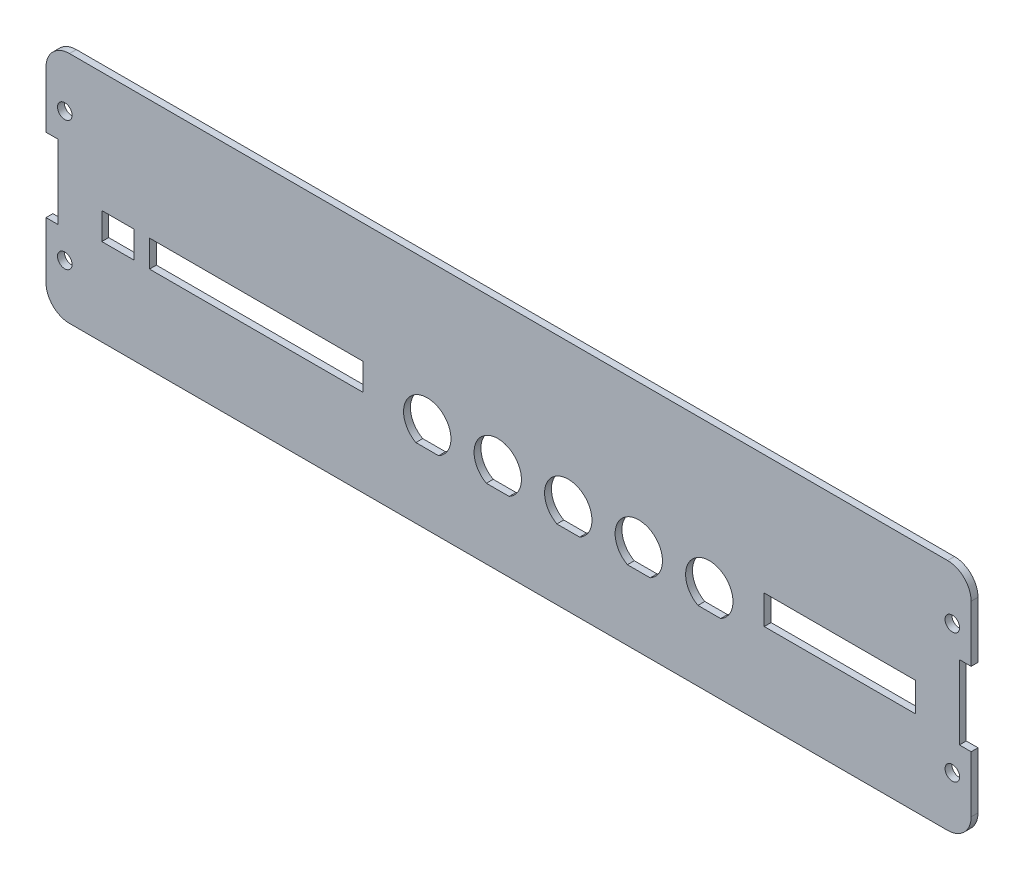
SolidWorks part; units mm, degrees
ref_plane "Front Plane" through (0, 0, 0) normal (0, 0, 1) x (1, 0, 0)
ref_plane "Top Plane" through (0, 0, 0) normal (0, 1, 0) x (1, 0, 0)
ref_plane "Right Plane" through (0, 0, 0) normal (1, 0, 0) x (0, 0, -1)
sketch "Sketch2" plane through (0, 0, 0) normal (0, 0, 1) x (1, 0, 0)
  line L0 (118.618, 31.5722) -> (-118.618, 31.5722)
  line L1 (-124.968, 25.2222) -> (-124.968, 9.9822)
  line L2 (-124.968, 9.9822) -> (-121.793, 9.9822)
  line L3 (-121.793, 9.9822) -> (-121.793, -9.9822)
  line L4 (0, 0) -> (0, 31.5722) construction
  line L5 (0, 0) -> (-121.793, 0) construction
  line L6 (124.968, 25.2222) -> (124.968, 9.9822)
  line L7 (124.968, 9.9822) -> (121.793, 9.9822)
  line L8 (121.793, 9.9822) -> (121.793, -9.9822)
  line L9 (124.968, -9.9822) -> (121.793, -9.9822)
  line L10 (124.968, -25.2222) -> (124.968, -9.9822)
  line L11 (-124.968, -9.9822) -> (-121.793, -9.9822)
  line L12 (-124.968, -25.2222) -> (-124.968, -9.9822)
  line L13 (118.618, -31.5722) -> (-118.618, -31.5722)
  arc A0 (-124.968, 25.2222) -> (-118.618, 31.5722) centre (-118.618, 25.2222) cw
  arc A1 (124.968, 25.2222) -> (118.618, 31.5722) centre (118.618, 25.2222) ccw
  arc A2 (124.968, -25.2222) -> (118.618, -31.5722) centre (118.618, -25.2222) cw
  arc A3 (-124.968, -25.2222) -> (-118.618, -31.5722) centre (-118.618, -25.2222) ccw
  point P22 (121.793, 0)
  point P25 (-124.968, -17.6022)
  dimension "D1" = 6.35
  dimension "D2" = 3.175
  dimension "D3" = 21.59
  dimension "D4" = 9.9822
  dimension "D5" = 249.936
extrude "MainBody" add sketch "Sketch2" along normal blind 1.8542
sketch "Sketch3" plane through (0, 0, 1.8542) normal (0, 0, 1) x (1, 0, 0)
  line L0 (118.618, 31.5722) -> (-118.618, 31.5722) construction
  line L2 (0, 31.5722) -> (0, 0) construction
  line L3 (0, 0) -> (-121.793, 0) construction
  line L4 (-121.793, 9.9822) -> (-121.793, -9.9822) construction
  circle A0 centre (-119.888, 17.4625) radius 1.9685
  circle A1 centre (119.888, 17.4625) radius 1.9685
  circle A2 centre (119.888, -17.4625) radius 1.9685
  circle A3 centre (-119.888, -17.4625) radius 1.9685
  dimension "D1" = 3.937
  dimension "D2" = 17.4625
  dimension "D3" = 119.888
extrude "MountHoles" cut sketch "Sketch3" against normal through all
ref_axis "MntTopLeft" through (-119.888, 17.4625, 0) along (0, 0, 1)
ref_axis "MntBottomLeft" through (-119.888, -17.4625, 0) along (0, 0, 1)
ref_axis "MntTopRight" through (119.888, 17.4625, 0) along (0, 0, 1)
ref_axis "MntBottomRight" through (119.888, -17.4625, 0) along (0, 0, 1)
ref_plane "ExtFront" through (0, 0, 1.8542) normal (0, 0, 1) x (1, 0, 0)
ref_plane "IntFront" through (0, 0, 0) normal (0, 0, -1) x (-1, 0, 0)
ref_plane "TBCenter" through (0, 0, 0) normal (0, 1, 0) x (1, 0, 0)
ref_plane "LRCenter" through (0, 0, 0) normal (-1, 0, 0) x (0, 0, 1)
sketch "Sketch4" plane through (0, 0, 1.8542) normal (0, 0, 1) x (1, 0, 0)
  line L12 (51.1533, -12.6575) -> (57.3047, -12.6575)
  line L13 (51.1533, -12.6575) -> (57.3047, -12.6575)
  line L14 (69.068, -0.7936) -> (69.068, -8.6476)
  line L15 (110.002, -0.7936) -> (69.068, -0.7936)
  line L16 (110.002, -8.6476) -> (110.002, -0.7936)
  line L17 (69.068, -8.6476) -> (110.002, -8.6476)
  line L18 (69.068, -0.7936) -> (69.068, -8.6476)
  line L19 (110.002, -0.7936) -> (69.068, -0.7936)
  line L20 (110.002, -8.6476) -> (110.002, -0.7936)
  line L21 (69.068, -8.6476) -> (110.002, -8.6476)
  line L24 (32.1033, -12.6575) -> (38.2547, -12.6575)
  line L25 (32.1033, -12.6575) -> (38.2547, -12.6575)
  line L28 (13.0533, -12.6575) -> (19.2047, -12.6575)
  line L29 (13.0533, -12.6575) -> (19.2047, -12.6575)
  line L31 (-5.9967, -12.6575) -> (0.1547, -12.6575)
  line L32 (-5.9967, -12.6575) -> (0.1547, -12.6575)
  line L35 (-25.0467, -12.6575) -> (-18.8953, -12.6575)
  line L36 (-25.0467, -12.6575) -> (-18.8953, -12.6575)
  line L73 (-96.998, -0.7936) -> (-96.998, -8.0476)
  line L74 (-39.344, -0.7936) -> (-96.998, -0.7936)
  line L75 (-96.998, -8.0476) -> (-39.344, -8.0476)
  line L76 (-39.344, -8.0476) -> (-39.344, -0.7936)
  line L77 (-96.998, -0.7936) -> (-96.998, -8.0476)
  line L78 (-39.344, -0.7936) -> (-96.998, -0.7936)
  line L79 (-96.998, -8.0476) -> (-39.344, -8.0476)
  line L80 (-39.344, -8.0476) -> (-39.344, -0.7936)
  line L91 (-109.892, -0.7936) -> (-109.892, -8.0476)
  line L92 (-101.238, -0.7936) -> (-109.892, -0.7936)
  line L93 (-101.238, -8.0476) -> (-101.238, -0.7936)
  line L94 (-109.892, -8.0476) -> (-101.238, -8.0476)
  line L95 (-109.892, -0.7936) -> (-109.892, -8.0476)
  line L96 (-101.238, -0.7936) -> (-109.892, -0.7936)
  line L97 (-101.238, -8.0476) -> (-101.238, -0.7936)
  line L98 (-109.892, -8.0476) -> (-101.238, -8.0476)
  arc A3 (57.3047, -12.6575) -> (51.1533, -12.6575) centre (54.229, -7.0441) ccw
  arc A4 (57.3047, -12.6575) -> (51.1533, -12.6575) centre (54.229, -7.0441) ccw
  arc A6 (38.2547, -12.6575) -> (32.1033, -12.6575) centre (35.179, -7.0441) ccw
  arc A7 (38.2547, -12.6575) -> (32.1033, -12.6575) centre (35.179, -7.0441) ccw
  arc A9 (19.2047, -12.6575) -> (13.0533, -12.6575) centre (16.129, -7.0441) ccw
  arc A10 (19.2047, -12.6575) -> (13.0533, -12.6575) centre (16.129, -7.0441) ccw
  arc A13 (0.1547, -12.6575) -> (-5.9967, -12.6575) centre (-2.921, -7.0441) ccw
  arc A14 (0.1547, -12.6575) -> (-5.9967, -12.6575) centre (-2.921, -7.0441) ccw
  arc A16 (-18.8953, -12.6575) -> (-25.0467, -12.6575) centre (-21.971, -7.0441) ccw
  arc A17 (-18.8953, -12.6575) -> (-25.0467, -12.6575) centre (-21.971, -7.0441) ccw
  dimension "D1" = 0.127
  dimension "D2" = 0.127
  dimension "D3" = 0.127
  dimension "D4" = 0.127
  dimension "D5" = 0.127
  dimension "D6" = 0.127
  dimension "D7" = 0.127
  dimension "D8" = 0.127
extrude "Cut-Extrude1" cut sketch "Sketch4" against normal up to next
equation "\"MainBodyExtWidth\"=9.84"
equation "\"MainBodyExtHeight\"=2.52"
equation "\"D4@Sketch2\"=0.786/2in"
equation "\"D5@Sketch2\"=\"MainBodyExtWidth\""
equation "\"MainBodyThickness\"= 0.073"
equation "\"D1@MainBody\" = \"MainBodyThickness\""
equation "\"ScrewMountSize\"=0.155"
equation "\"D1@Sketch3\"=\"ScrewMountSize\""
